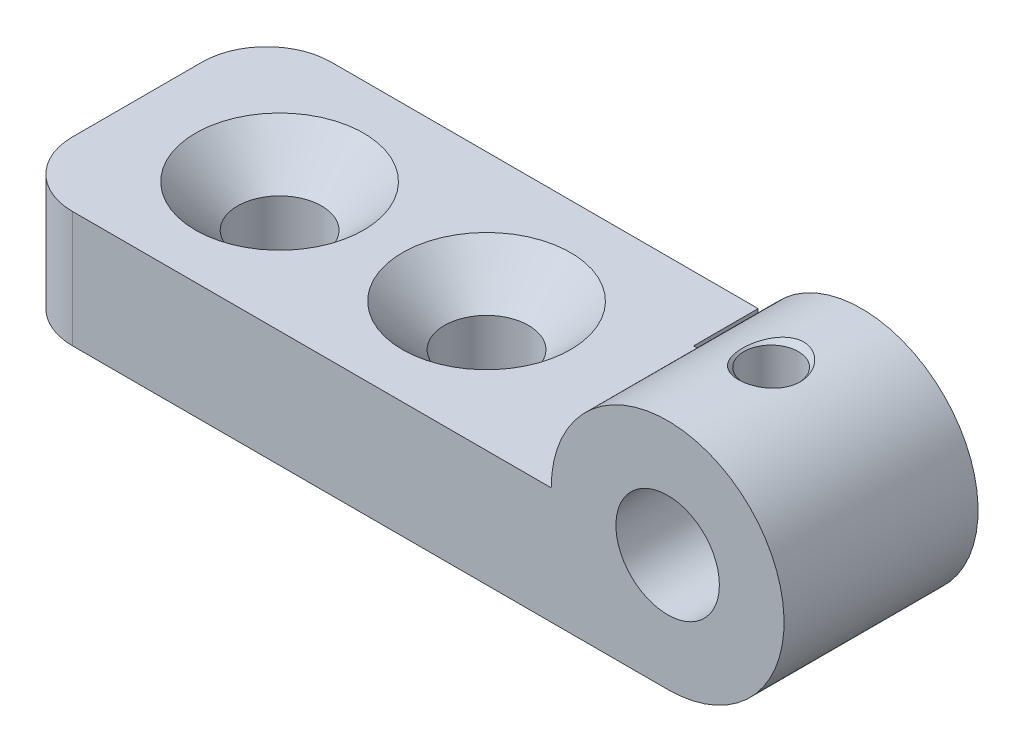
SolidWorks part; units mm, degrees
ref_plane "前视基准面" through (0, 0, 0) normal (0, 0, 1) x (1, 0, 0)
ref_plane "上视基准面" through (0, 0, 0) normal (0, 1, 0) x (1, 0, 0)
ref_plane "右视基准面" through (0, 0, 0) normal (1, 0, 0) x (0, 0, -1)
sketch "草图1" plane through (0, 0, 0) normal (0, 0, 1) x (1, 0, 0)
  line L0 (42, 9) -> (51, 9) construction
  line L1 (0, 0) -> (51, 0)
  line L2 (0, 0) -> (0, 9)
  line L3 (0, 9) -> (42, 9)
  line L4 (51, 0) -> (51, 9) construction
  arc A0 (51, 0) -> (42, 9) centre (51, 9) ccw
  arc A1 (42, 9) -> (51, 0) centre (51, 9) ccw construction
  circle A2 centre (51, 9) radius 4
  dimension "D1" = 9
  dimension "D4" = 8
  dimension "D2" = 9
  dimension "D3" = 51
extrude "凸台-拉伸1" add sketch "草图1" along normal mid plane 20
sketch "草图2" plane through (0, 9, 0) normal (0, 1, 0) x (1, 0, 0)
  line L0 (60, 5) -> (38, 5)
  line L1 (60, -10) -> (60, 10) construction
  line L2 (38, 5) -> (38, 10)
  line L3 (42, 10) -> (0, 10) construction
  line L4 (42, -10) -> (0, -10) construction
  line L5 (0, -9.5429) -> (0, 9.5429) construction
  dimension "D1" = 15
  dimension "D2" = 38
extrude "切除-拉伸1" cut sketch "草图2" against normal through all both and the other way through all flip side to cut
hole_wizard "Ø6.5 (6.5) 直径孔1" positions "草图5" profile "草图6" hole size "Ø6.5" standard "GB"
sketch "草图5" plane through (0, 9, 0) normal (0, 1, 0) x (1, 0, 0)
  line L0 (-9.9, 0) -> (9.9, 0) construction
  line L1 (38, 5) -> (38, 10) construction
  point P0 (11, 0)
  point P4 (27, 0)
  dimension "D1" = 16
  dimension "D2" = 11
sketch "草图6" plane through (11, 9, 0) normal (1, 0, 0) x (0, 0, 1)
  line L0 (0, 0) -> (0, 14.9528)
  line L1 (0, 14.9528) -> (3.25, 13)
  line L2 (3.25, 13) -> (3.25, 3.25)
  line L3 (3.25, 3.25) -> (6.5, 0)
  line L5 (6.5, 0) -> (0, 0)
  line L6 (-3.25, 3.25) -> (-6.5, 0) construction
  line L10 (0, 14.9528) -> (-3.25, 13) construction
  line L11 (0, -6.35) -> (0, 107.95) construction
  dimension "孔直径" = 6.5
  dimension "孔深度" = 13
  dimension "近端锥形沉头孔直径" = 13
  dimension "近端锥形沉头孔角度" = 90
  dimension "导头角度" = 118
hole_wizard "M5 螺纹孔1" positions "3D草图1" profile "草图7" tap size "M5" standard "GB" end condition up to next
sketch3d "3D草图1"
  line L0 (51, 18, 2) -> (51, 11.5502, 2) construction
  point P0 (51, 18, 2)
  dimension "D1" = 8
sketch "草图7" plane through (51, 18, 2) normal (1, 0, 0) x (0, 0, 1)
  line L0 (0, 0) -> (0, 5)
  line L1 (0, 5) -> (2.1, 5)
  line L2 (2.1, 5) -> (2.1, 0.425)
  line L3 (2.1, 0.425) -> (2.525, 0)
  line L5 (2.525, 0) -> (0, 0)
  line L6 (-2.1, 0.425) -> (-2.525, 0) construction
  line L11 (0, -6.35) -> (0, 107.95) construction
  dimension "通孔螺纹孔钻头直径" = 4.2
  dimension "通孔螺纹孔钻头深度" = 5
  dimension "近端锥形沉头孔直径" = 5.05
  dimension "近端锥形沉头孔角度" = 90
cosmetic thread "孔螺纹线1" parameters "D2"=5
fillet "圆角1" radius 5 2 edges at (0, 4.5, -10) (0, 4.5, 10)
